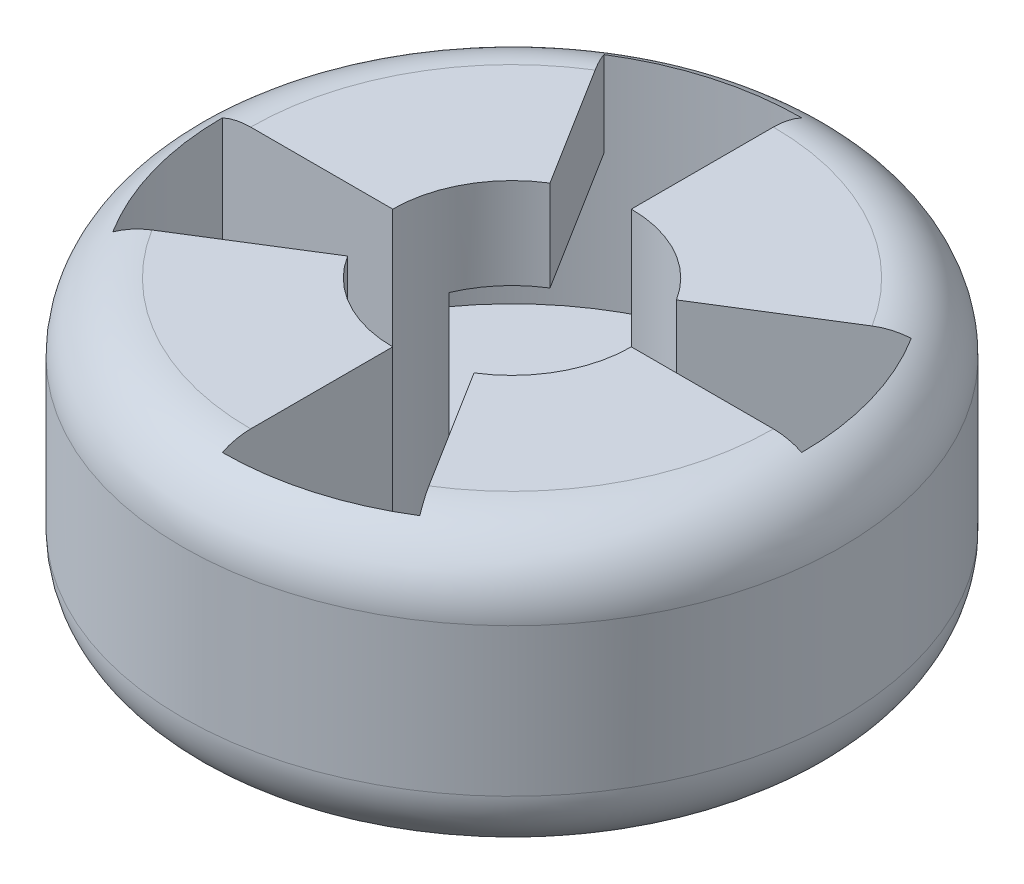
SolidWorks part; units mm, degrees
ref_plane "Front Plane" through (0, 0, 0) normal (0, 0, 1) x (1, 0, 0)
ref_plane "Top Plane" through (0, 0, 0) normal (0, 1, 0) x (1, 0, 0)
ref_plane "Right Plane" through (0, 0, 0) normal (1, 0, 0) x (0, 0, -1)
sketch "Sketch2" plane through (0, 0, 0) normal (1, 0, 0) x (0, 0, -1)
  line L0 (-5.25, 0) -> (-14.5, 0)
  line L1 (-14.5, 0) -> (-14.5, 12.5)
  line L3 (0, 31) -> (0, 21) construction
  line L6 (-14.5, 12.5) -> (-5.25, 12.5)
  line L7 (-5.25, 12.5) -> (-5.25, 0)
  point P3 (-25, 15)
  point P7 (-24.4271, 15)
  dimension "D1" = 14.5
  dimension "D2" = 5.25
  dimension "D3" = 12.5
revolve "Revolve1" add sketch "Sketch2" angle 360 about L3
sketch "Sketch3" plane through (0, 12.5, 0) normal (0, 1, 0) x (1, 0, 0)
  line L2 (-6.7565, 10.8126) -> (0, 0)
  line L5 (0, 12.75) -> (0, 0)
  arc A1 (0, 12.75) -> (-6.7565, 10.8126) centre (0, 0) ccw
  point P0 (0, 0)
  dimension "D2" = 12.75
  dimension "D1" = 32
extrude "Cut-Extrude1" cut sketch "Sketch3" against normal blind 10
pattern_circular "CirPattern1" count 4 over 360 about axis through (0, 12.5, 0) along (0, 1, 0) of "Cut-Extrude1"
sketch "Sketch4" plane through (0, 2.5, 0) normal (0, 1, 0) x (1, 0, 0)
  line L2 (5.25, 0) -> (12.75, 0)
  line L3 (10.8126, 6.7565) -> (4.4523, 2.7821)
  line L4 (5.25, 0) -> (12.75, 0)
  line L5 (10.8126, 6.7565) -> (4.4523, 2.7821)
  line L6 (-5.25, 0) -> (-12.75, 0)
  line L7 (-10.8126, -6.7565) -> (-4.4523, -2.7821)
  line L8 (-5.25, 0) -> (-12.75, 0)
  line L9 (-10.8126, -6.7565) -> (-4.4523, -2.7821)
  arc A2 (12.75, 0) -> (10.8126, 6.7565) centre (0, 0) ccw
  arc A3 (5.25, 0) -> (4.4523, 2.7821) centre (0, 0) ccw
  arc A5 (5.25, 0) -> (4.4523, 2.7821) centre (0, 0) ccw
  arc A6 (-12.75, 0) -> (-10.8126, -6.7565) centre (0, 0) ccw
  arc A7 (-5.25, 0) -> (-4.4523, -2.7821) centre (0, 0) ccw
  arc A9 (-5.25, 0) -> (-4.4523, -2.7821) centre (0, 0) ccw
  arc A13 (12.75, 0) -> (10.8126, 6.7565) centre (0, 0) ccw
  arc A14 (-12.75, 0) -> (-10.8126, -6.7565) centre (0, 0) ccw
  dimension "D1" = 0
  dimension "D2" = 0
extrude "Cut-Extrude2" cut sketch "Sketch4" against normal blind 10
sketch "Sketch5" plane through (0, 2.5, 0) normal (0, 1, 0) x (1, 0, 0)
  line L0 (0, 0) -> (-6.7565, 10.8126)
  line L1 (0, 0) -> (-11.7364, 4.9818)
  arc A0 (-6.7565, 10.8126) -> (-11.7364, 4.9818) centre (0, 0) ccw
  dimension "D1" = 35
extrude "Cut-Extrude3" cut sketch "Sketch5" along normal blind 6
pattern_circular "CirPattern2" count 2 over 360 about axis through (0, 12.5, 0) along (0, 1, 0) of "Cut-Extrude3"
fillet "Fillet1" radius 3 2 edges at (0, 12.5, 14.5) (0, 0, 14.5)
